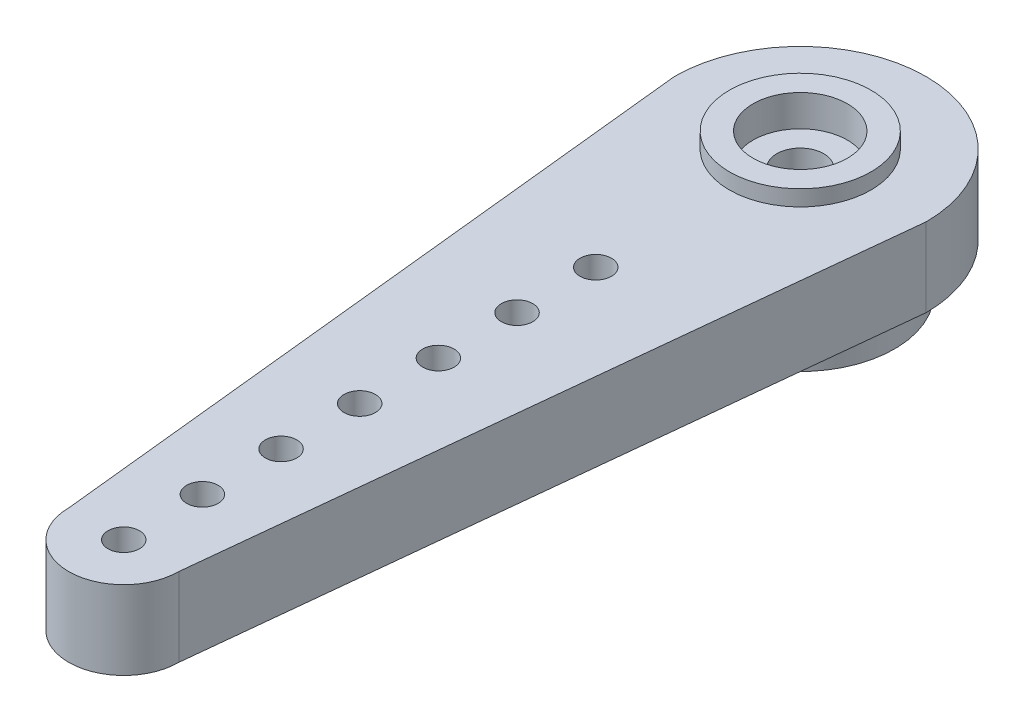
SolidWorks part; units mm, degrees
material "ABS"
ref_plane "Front Plane" through (0, 0, 0) normal (0, 0, 1) x (1, 0, 0)
ref_plane "Top Plane" through (0, 0, 0) normal (0, 1, 0) x (1, 0, 0)
ref_plane "Right Plane" through (0, 0, 0) normal (1, 0, 0) x (0, 0, -1)
sketch "Sketch1" plane through (0, 0, 0) normal (0, 1, 0) x (1, 0, 0)
  circle A0 centre (0, 0) radius 6
  dimension "D1" = 12
extrude "Boss-Extrude1" add sketch "Sketch1" along normal blind 3
sketch "Sketch7" plane through (0, 0, 0) normal (0, -1, 0) x (1, 0, 0)
  line L0 (0, 3.75) -> (0, 3.05) construction
  line L1 (0, 3.05) -> (0.7, 3.6841)
  line L2 (0, 3.05) -> (-0.7, 3.6841)
  line L3 (1.2405, 2.7863) -> (2.1379, 3.0809)
  line L4 (1.2405, 2.7863) -> (0.859, 3.6503)
  line L5 (2.2666, 2.0408) -> (3.2062, 1.9449)
  line L6 (2.2666, 2.0408) -> (2.2694, 2.9853)
  line L7 (2.9007, 0.9425) -> (3.7201, 0.4727)
  line L8 (2.9007, 0.9425) -> (3.2875, 1.8042)
  line L9 (3.0333, -0.3188) -> (3.5907, -1.0813)
  line L10 (3.0333, -0.3188) -> (3.7371, 0.3111)
  line L11 (2.6414, -1.525) -> (2.8405, -2.4483)
  line L12 (2.6414, -1.525) -> (3.5405, -1.2358)
  line L13 (1.7927, -2.4675) -> (1.5991, -3.3919)
  line L14 (1.7927, -2.4675) -> (2.7318, -2.569)
  line L15 (0.6341, -2.9834) -> (0.0813, -3.7491)
  line L16 (0.6341, -2.9834) -> (1.4507, -3.458)
  line L17 (-0.6341, -2.9834) -> (-1.4507, -3.458)
  line L18 (-0.6341, -2.9834) -> (-0.0813, -3.7491)
  line L19 (-1.7927, -2.4675) -> (-2.7318, -2.569)
  line L20 (-1.7927, -2.4675) -> (-1.5991, -3.3919)
  line L21 (-2.6414, -1.525) -> (-3.5405, -1.2358)
  line L22 (-2.6414, -1.525) -> (-2.8405, -2.4483)
  line L23 (-3.0333, -0.3188) -> (-3.7371, 0.3111)
  line L24 (-3.0333, -0.3188) -> (-3.5907, -1.0813)
  line L25 (-2.9007, 0.9425) -> (-3.2875, 1.8042)
  line L26 (-2.9007, 0.9425) -> (-3.7201, 0.4727)
  line L27 (-2.2666, 2.0408) -> (-2.2694, 2.9853)
  line L28 (-2.2666, 2.0408) -> (-3.2062, 1.9449)
  line L29 (-1.2405, 2.7863) -> (-0.859, 3.6503)
  line L30 (-1.2405, 2.7863) -> (-2.1379, 3.0809)
  circle A0 centre (0, 0) radius 3.75 construction
  arc A1 (-0.7, 3.6841) -> (0.7, 3.6841) centre (0, 0) cw construction
  arc A2 (0.7, 3.6841) -> (0.9, 3.6404) centre (0, 0) cw
  arc A3 (2.1379, 3.0809) -> (2.3029, 2.9596) centre (0, 0) cw
  arc A4 (3.2062, 1.9449) -> (3.3076, 1.7671) centre (0, 0) cw
  arc A5 (3.7201, 0.4727) -> (3.7403, 0.269) centre (0, 0) cw
  arc A6 (3.5907, -1.0813) -> (3.5264, -1.2756) centre (0, 0) cw
  arc A7 (2.8405, -2.4483) -> (2.7027, -2.5996) centre (0, 0) cw
  arc A8 (1.5991, -3.3919) -> (1.4117, -3.4742) centre (0, 0) cw
  arc A9 (0.0813, -3.7491) -> (-0.1235, -3.748) centre (0, 0) cw
  arc A10 (-1.4507, -3.458) -> (-1.6372, -3.3737) centre (0, 0) cw
  arc A11 (-2.7318, -2.569) -> (-2.8679, -2.4161) centre (0, 0) cw
  arc A12 (-3.5405, -1.2358) -> (-3.6027, -1.0408) centre (0, 0) cw
  arc A13 (-3.7371, 0.3111) -> (-3.7145, 0.5145) centre (0, 0) cw
  arc A14 (-3.2875, 1.8042) -> (-3.1841, 1.9809) centre (0, 0) cw
  arc A15 (-2.2694, 2.9853) -> (-2.1031, 3.1047) centre (0, 0) cw
  arc A16 (-0.859, 3.6503) -> (-0.6585, 3.6917) centre (0, 0) cw
  point P64 (0, 0)
extrude "Cut-Extrude4" cut sketch "Sketch7" against normal through all contours A16 L29 L30 A15 L27 L28 A14 L25 L26 A13 L23 L24 A12 L21 L22 A11 L19 L20 A10 L17 L18 A9 L15 L16 A8 L13 L14 A7 L11 L12 A6 L9 L10 A5 L7 L8 A4 L5 L6 A3 L3 L4 A2 L1 L2 region at (0, 0, 0)
sketch "Sketch2" plane through (0, 3, 0) normal (0, 1, 0) x (1, 0, 0)
  line L0 (8, 0) -> (3.5, -43)
  line L1 (-8, 0) -> (-3.5, -43)
  arc A0 (8, 0) -> (-8, 0) centre (0, 0) ccw
  arc A1 (-3.5, -43) -> (3.5, -43) centre (0, -43) ccw
  dimension "D1" = 16
  dimension "D2" = 7
  dimension "D3" = 43
extrude "Boss-Extrude2" add sketch "Sketch2" along normal blind 5
sketch "Sketch3" plane through (0, 8, 0) normal (0, 1, 0) x (1, 0, 0)
  circle A0 centre (0, 0) radius 4.5
  dimension "D1" = 9
extrude "Boss-Extrude3" add sketch "Sketch3" along normal blind 1
sketch "Sketch4" plane through (0, 9, 0) normal (0, 1, 0) x (1, 0, 0)
  circle A0 centre (0, 0) radius 3
  dimension "D1" = 6
extrude "Cut-Extrude1" cut sketch "Sketch4" against normal blind 2
sketch "Sketch5" plane through (0, 7, 0) normal (0, 1, 0) x (1, 0, 0)
  circle A0 centre (0, 0) radius 1.5
  dimension "D1" = 3
extrude "Cut-Extrude2" cut sketch "Sketch5" against normal through all
sketch "Sketch6" plane through (0, 8, 0) normal (0, 1, 0) x (1, 0, 0)
  line L0 (0, -4.5) -> (0, -18.9486) construction
  circle A0 centre (0, -13) radius 1
  circle A1 centre (0, 0) radius 3 construction
  circle A3 centre (0, 0) radius 4.5 construction
  circle A4 centre (0, 0) radius 4.5 construction
  circle A5 centre (0, -18) radius 1
  circle A6 centre (0, -23) radius 1
  circle A7 centre (0, -28) radius 1
  circle A8 centre (0, -33) radius 1
  circle A9 centre (0, -38) radius 1
  circle A10 centre (0, -43) radius 1
  dimension "D1" = 2
  dimension "D2" = 13
  dimension "D3" = 7
extrude "Cut-Extrude3" cut sketch "Sketch6" against normal blind 10
sketch "Sketch8" plane through (0, 3, 0) normal (0, -1, 0) x (1, 0, 0)
  line L30 (-0.859, 3.6503) -> (-1.2405, 2.7863)
  line L31 (-1.2405, 2.7863) -> (-2.1379, 3.0809)
  line L32 (-2.2694, 2.9853) -> (-2.2666, 2.0408)
  line L33 (-2.2666, 2.0408) -> (-3.2062, 1.9449)
  line L34 (-3.2875, 1.8042) -> (-2.9007, 0.9425)
  line L35 (-2.9007, 0.9425) -> (-3.7201, 0.4727)
  line L36 (-3.7371, 0.3111) -> (-3.0333, -0.3188)
  line L37 (-3.0333, -0.3188) -> (-3.5907, -1.0813)
  line L38 (-3.5405, -1.2358) -> (-2.6414, -1.525)
  line L39 (-2.6414, -1.525) -> (-2.8405, -2.4483)
  line L40 (-2.7318, -2.569) -> (-1.7927, -2.4675)
  line L41 (-1.7927, -2.4675) -> (-1.5991, -3.3919)
  line L42 (-1.4507, -3.458) -> (-0.6341, -2.9834)
  line L43 (-0.6341, -2.9834) -> (-0.0813, -3.7491)
  line L44 (0.0813, -3.7491) -> (0.6341, -2.9834)
  line L45 (0.6341, -2.9834) -> (1.4507, -3.458)
  line L46 (1.5991, -3.3919) -> (1.7927, -2.4675)
  line L47 (1.7927, -2.4675) -> (2.7318, -2.569)
  line L48 (2.8405, -2.4483) -> (2.6414, -1.525)
  line L49 (2.6414, -1.525) -> (3.5405, -1.2358)
  line L50 (3.5907, -1.0813) -> (3.0333, -0.3188)
  line L51 (3.0333, -0.3188) -> (3.7371, 0.3111)
  line L52 (3.7201, 0.4727) -> (2.9007, 0.9425)
  line L53 (2.9007, 0.9425) -> (3.2875, 1.8042)
  line L54 (3.2062, 1.9449) -> (2.2666, 2.0408)
  line L55 (2.2666, 2.0408) -> (2.2694, 2.9853)
  line L56 (2.1379, 3.0809) -> (1.2405, 2.7863)
  line L57 (1.2405, 2.7863) -> (0.859, 3.6503)
  line L58 (0.7, 3.6841) -> (0, 3.05)
  line L59 (0, 3.05) -> (-0.7, 3.6841)
  line L60 (-0.859, 3.6503) -> (-1.2405, 2.7863)
  line L61 (-1.2405, 2.7863) -> (-2.1379, 3.0809)
  line L62 (-2.2694, 2.9853) -> (-2.2666, 2.0408)
  line L63 (-2.2666, 2.0408) -> (-3.2062, 1.9449)
  line L64 (-3.2875, 1.8042) -> (-2.9007, 0.9425)
  line L65 (-2.9007, 0.9425) -> (-3.7201, 0.4727)
  line L66 (-3.7371, 0.3111) -> (-3.0333, -0.3188)
  line L67 (-3.0333, -0.3188) -> (-3.5907, -1.0813)
  line L68 (-3.5405, -1.2358) -> (-2.6414, -1.525)
  line L69 (-2.6414, -1.525) -> (-2.8405, -2.4483)
  line L70 (-2.7318, -2.569) -> (-1.7927, -2.4675)
  line L71 (-1.7927, -2.4675) -> (-1.5991, -3.3919)
  line L72 (-1.4507, -3.458) -> (-0.6341, -2.9834)
  line L73 (-0.6341, -2.9834) -> (-0.0813, -3.7491)
  line L74 (0.0813, -3.7491) -> (0.6341, -2.9834)
  line L75 (0.6341, -2.9834) -> (1.4507, -3.458)
  line L76 (1.5991, -3.3919) -> (1.7927, -2.4675)
  line L77 (1.7927, -2.4675) -> (2.7318, -2.569)
  line L78 (2.8405, -2.4483) -> (2.6414, -1.525)
  line L79 (2.6414, -1.525) -> (3.5405, -1.2358)
  line L80 (3.5907, -1.0813) -> (3.0333, -0.3188)
  line L81 (3.0333, -0.3188) -> (3.7371, 0.3111)
  line L82 (3.7201, 0.4727) -> (2.9007, 0.9425)
  line L83 (2.9007, 0.9425) -> (3.2875, 1.8042)
  line L84 (3.2062, 1.9449) -> (2.2666, 2.0408)
  line L85 (2.2666, 2.0408) -> (2.2694, 2.9853)
  line L86 (2.1379, 3.0809) -> (1.2405, 2.7863)
  line L87 (1.2405, 2.7863) -> (0.859, 3.6503)
  line L88 (0.7, 3.6841) -> (0, 3.05)
  line L89 (0, 3.05) -> (-0.7, 3.6841)
  circle A0 centre (0, 0) radius 1.5 construction
  circle A1 centre (0, 0) radius 1.5
  arc A15 (-0.7, 3.6841) -> (-0.859, 3.6503) centre (0, 0) ccw
  arc A16 (-2.1379, 3.0809) -> (-2.2694, 2.9853) centre (0, 0) ccw
  arc A17 (-3.2062, 1.9449) -> (-3.2875, 1.8042) centre (0, 0) ccw
  arc A18 (-3.7201, 0.4727) -> (-3.7371, 0.3111) centre (0, 0) ccw
  arc A19 (-3.5907, -1.0813) -> (-3.5405, -1.2358) centre (0, 0) ccw
  arc A20 (-2.8405, -2.4483) -> (-2.7318, -2.569) centre (0, 0) ccw
  arc A21 (-1.5991, -3.3919) -> (-1.4507, -3.458) centre (0, 0) ccw
  arc A22 (-0.0813, -3.7491) -> (0.0813, -3.7491) centre (0, 0) ccw
  arc A23 (1.4507, -3.458) -> (1.5991, -3.3919) centre (0, 0) ccw
  arc A24 (2.7318, -2.569) -> (2.8405, -2.4483) centre (0, 0) ccw
  arc A25 (3.5405, -1.2358) -> (3.5907, -1.0813) centre (0, 0) ccw
  arc A26 (3.7371, 0.3111) -> (3.7201, 0.4727) centre (0, 0) ccw
  arc A27 (3.2875, 1.8042) -> (3.2062, 1.9449) centre (0, 0) ccw
  arc A28 (2.2694, 2.9853) -> (2.1379, 3.0809) centre (0, 0) ccw
  arc A29 (0.859, 3.6503) -> (0.7, 3.6841) centre (0, 0) ccw
  arc A30 (-0.7, 3.6841) -> (-0.859, 3.6503) centre (0, 0) ccw
  arc A31 (-2.1379, 3.0809) -> (-2.2694, 2.9853) centre (0, 0) ccw
  arc A32 (-3.2062, 1.9449) -> (-3.2875, 1.8042) centre (0, 0) ccw
  arc A33 (-3.7201, 0.4727) -> (-3.7371, 0.3111) centre (0, 0) ccw
  arc A34 (-3.5907, -1.0813) -> (-3.5405, -1.2358) centre (0, 0) ccw
  arc A35 (-2.8405, -2.4483) -> (-2.7318, -2.569) centre (0, 0) ccw
  arc A36 (-1.5991, -3.3919) -> (-1.4507, -3.458) centre (0, 0) ccw
  arc A37 (-0.0813, -3.7491) -> (0.0813, -3.7491) centre (0, 0) ccw
  arc A38 (1.4507, -3.458) -> (1.5991, -3.3919) centre (0, 0) ccw
  arc A39 (2.7318, -2.569) -> (2.8405, -2.4483) centre (0, 0) ccw
  arc A40 (3.5405, -1.2358) -> (3.5907, -1.0813) centre (0, 0) ccw
  arc A41 (3.7371, 0.3111) -> (3.7201, 0.4727) centre (0, 0) ccw
  arc A42 (3.2875, 1.8042) -> (3.2062, 1.9449) centre (0, 0) ccw
  arc A43 (2.2694, 2.9853) -> (2.1379, 3.0809) centre (0, 0) ccw
  arc A44 (0.859, 3.6503) -> (0.7, 3.6841) centre (0, 0) ccw
  dimension "D1" = 0
extrude "Cut-Extrude5" cut sketch "Sketch8" against normal blind 2
